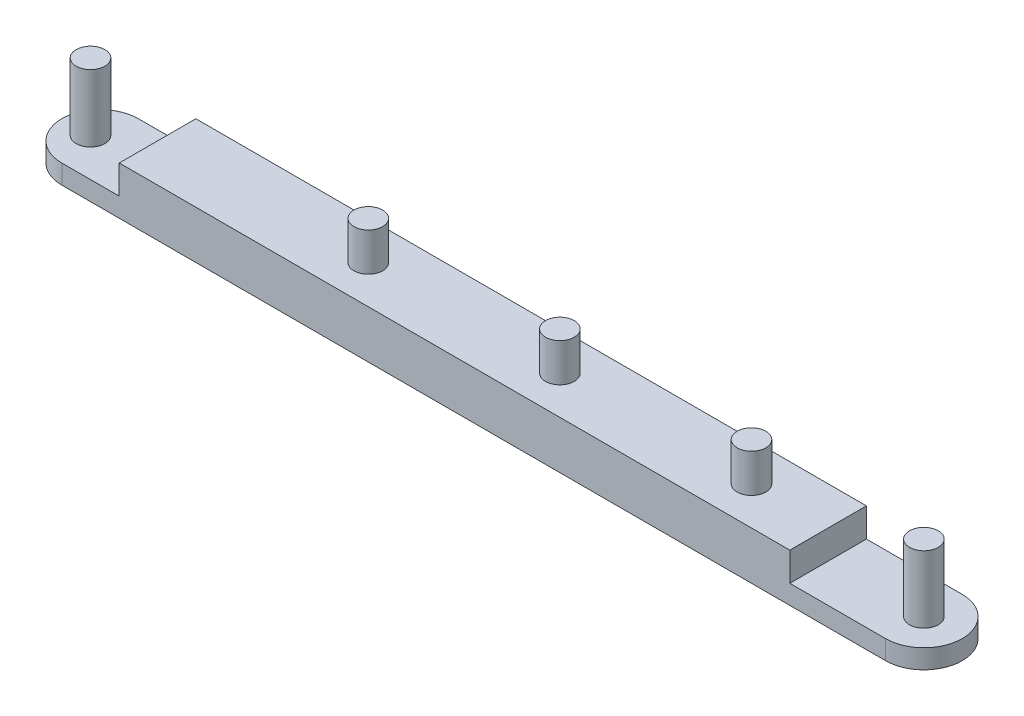
SolidWorks part; units mm, degrees
ref_plane "Front Plane" through (0, 0, 0) normal (0, 0, 1) x (1, 0, 0)
ref_plane "Top Plane" through (0, 0, 0) normal (0, 1, 0) x (1, 0, 0)
ref_plane "Right Plane" through (0, 0, 0) normal (1, 0, 0) x (0, 0, -1)
sketch "Sketch1" plane through (0, 0, 0) normal (0, 1, 0) x (1, 0, 0)
  line L0 (-25, -4) -> (65, -4)
  line L1 (65, 4) -> (-25, 4)
  line L2 (-25, 4) -> (-25, -4)
  arc A0 (65, -4) -> (65, 4) centre (65, 0) ccw
  dimension "D3" = 4
  dimension "D1" = 90
  dimension "D2" = 4
extrude "Boss-Extrude2" add sketch "Sketch1" along normal blind 2
sketch "Sketch3" plane through (0, 2, 0) normal (0, 1, 0) x (1, 0, 0)
  line L0 (-25, -4) -> (65, -4) construction
  line L1 (-25, 4) -> (55, 4)
  line L2 (-25, 4) -> (-25, -4)
  line L3 (-25, -4) -> (55, -4)
  line L4 (55, 4) -> (55, -4)
  dimension "D1" = 80
extrude "Boss-Extrude3" add sketch "Sketch3" along normal blind 3
sketch "Sketch4" plane through (0, 2, 0) normal (0, 1, 0) x (1, 0, 0)
  circle A0 centre (65, 0) radius 1.5
  dimension "D1" = 3
extrude "Boss-Extrude4" add sketch "Sketch4" along normal blind 7
sketch "Sketch12" plane through (0, 5, 0) normal (0, 1, 0) x (1, 0, 0)
  line L0 (55, -4) -> (55, 4) construction
  circle A0 centre (47, 0) radius 1.5
  circle A1 centre (27, 0) radius 1.5
  circle A2 centre (7, 0) radius 1.5
  dimension "D1" = 3
  dimension "D2" = 8
  dimension "D3" = 3
extrude "Boss-Extrude6" add sketch "Sketch12" along normal blind 4
sketch "Sketch14" plane through (0, 5, 0) normal (0, 1, 0) x (1, 0, 0)
  line L0 (-25, -4) -> (55, -4) construction
  line L1 (-25, 4) -> (-15, 4)
  line L2 (-25, 4) -> (-25, -4)
  line L3 (-25, -4) -> (-15, -4)
  line L4 (-15, 4) -> (-15, -4)
  dimension "D1" = 10
extrude "Cut-Extrude1" cut sketch "Sketch14" against normal blind 3
sketch "Sketch15" plane through (0, 2, 0) normal (0, 1, 0) x (1, 0, 0)
  line L0 (-25, 0) -> (-15, 0) construction
  line L1 (-25, 4) -> (-25, -4) construction
  line L2 (-15, -4) -> (-15, 4) construction
  circle A0 centre (-22, 0) radius 1.5
  dimension "D1" = 3
  dimension "D2" = 3
extrude "Boss-Extrude7" add sketch "Sketch15" along normal blind 7
fillet "Fillet1" radius 4 2 edges at (-25, 1, -4) (-25, 1, 4)
